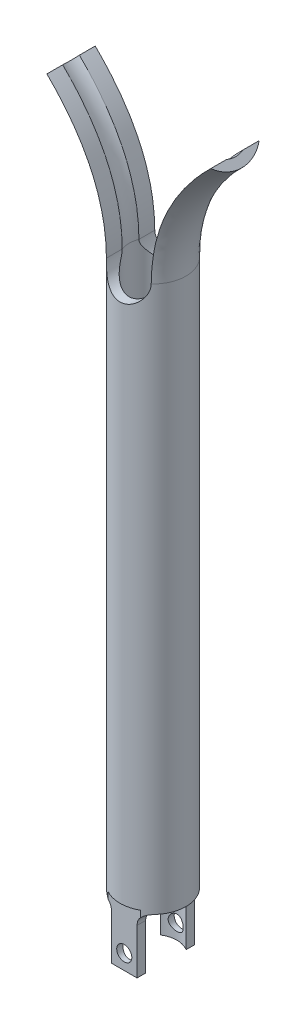
SolidWorks part; units mm, degrees
ref_plane "Front Plane" through (0, 0, 0) normal (0, 0, 1) x (1, 0, 0)
ref_plane "Top Plane" through (0, 0, 0) normal (0, 1, 0) x (1, 0, 0)
ref_plane "Right Plane" through (0, 0, 0) normal (1, 0, 0) x (0, 0, -1)
ref_axis "Axis1" through (0, -45, 0) along (0, 1, 0)
sketch "Sketch1" plane through (0, 0, 0) normal (0, 1, 0) x (1, 0, 0)
  circle A0 centre (0, 0) radius 1.0922
  dimension "D1" = 2.1844
extrude "Extrude-Thin1" add sketch "Sketch1" along normal blind 20 thin thin type one direction reverse wall 0.3
sketch "Sketch2" plane through (0, 20, 0) normal (0, 1, 0) x (1, 0, 0)
  arc A0 (-0.5732, -0.9297) -> (-0.2666, 1.0592) centre (0, 0) cw
  circle A1 centre (0, 0) radius 1.0922 construction
  arc A2 (-0.3687, -0.7011) -> (-0.1565, 0.7766) centre (0, 0) cw
  circle A3 centre (0, 0) radius 0.7922 construction
sketch "Sketch3" plane through (0, 20, 0) normal (0, 1, 0) x (1, 0, 0)
  line L0 (-0.7422, -0.277) -> (-0.7422, -0.8013)
  line L1 (-0.7422, 0.8013) -> (-0.7422, 0.277)
  line L2 (0, 0) -> (-1.0922, 0) construction
  arc A0 (-0.7422, -0.8013) -> (-0.7422, 0.8013) centre (0, 0) cw
  circle A1 centre (0, 0) radius 1.0922 construction
  arc A2 (-0.7422, -0.277) -> (-0.7422, 0.277) centre (0, 0) cw
  circle A5 centre (0, 0) radius 0.7922 construction
  arc A6 (-0.1565, 0.7766) -> (-0.3687, -0.7011) centre (0, 0) ccw construction
  dimension "D1" = 0.35
sketch "Sketch4" plane through (0, 0, 0) normal (0, 0, 1) x (1, 0, 0)
  line L3 (-1.0922, 20) -> (-1.1, 22.8198) construction
  line L4 (-1.1, 22.8198) -> (-4.0922, 25) construction
  spline S0 degree 2 poles (-1.0922, 20) (-1.1, 22.8198) (-4.0922, 25) knots 0 0 0 1 1 1
  dimension "D1" = 5
  dimension "D2" = 3
sweep "Sweep1" add profiles "Sketch3" path "Sketch4"
mirror "Mirror1" about plane through (0, 0, 0) normal (1, 0, 0) of "Sweep1"
sketch "Sketch5" plane through (0, 0, 0) normal (0, 0, 1) x (1, 0, 0)
  line L0 (0.7422, 20) -> (-0.7422, 20) construction
  circle A0 centre (0, 20) radius 0.7422
extrude "Cut-Extrude1" cut sketch "Sketch5" against normal through all both and the other way through all
sketch "Sketch6" plane through (0, 0, 0) normal (0, 0, 1) x (1, 0, 0)
  line L0 (1.0922, 0) -> (1.0922, 20) construction
  line L1 (1.0922, 18.2578) -> (-0.5078, 18.2578)
  line L2 (1.0922, 18.2578) -> (1.0922, 17.4578)
  line L3 (1.0922, 17.4578) -> (-0.5078, 17.4578)
  line L4 (-0.5078, 18.2578) -> (-0.5078, 17.4578)
  arc A1 (-0.7422, 20) -> (0.7422, 20) centre (0, 20) ccw construction
  point P6 (0, 19.2578)
  dimension "D1" = 1
  dimension "D2" = 1.6
  dimension "D3" = 0.8
extrude "Cut-Extrude2" [suppressed] cut sketch "Sketch6" against normal through all both and the other way through all
pattern_linear "LPattern1" [suppressed] count 4 spacing 1.2 of bodies 106
sketch "Sketch7" plane through (0, 0, 0) normal (0, 0, 1) x (1, 0, 0)
  line L0 (-3.9437, 25.3767) -> (-2.6955, 24.3236)
  line L1 (-2.6955, 24.3236) -> (-3.0029, 23.9592)
  line L2 (-3.0029, 23.9592) -> (-4.2334, 24.9973)
  line L3 (-4.2334, 24.9973) -> (-3.9437, 25.3767)
extrude "Cut-Extrude3" cut sketch "Sketch7" against normal blind 1 and the other way blind 1
mirror "Mirror2" about plane through (0, 0, 0) normal (1, 0, 0) of "Cut-Extrude3"
sketch "Sketch10" plane through (0, 0, 0) normal (0, -1, 0) x (1, 0, 0)
  line L0 (4.0304, 0) -> (-3.5992, 0) construction
  line L1 (4.0304, 0.9525) -> (-3.5992, 0.9525)
  line L2 (4.0304, 0.9525) -> (4.0304, -0.9525) construction
  line L3 (4.0304, -0.9525) -> (-3.5992, -0.9525)
  line L4 (-3.5992, 0.9525) -> (-3.5992, -0.9525) construction
  line L5 (1.0922, 0) -> (-1.0922, 0) construction
  line L6 (4.0304, 0.9525) -> (4.0304, 2.3773)
  line L7 (4.0304, 2.3773) -> (-3.5992, 2.3773)
  line L8 (-3.5992, 2.3773) -> (-3.5992, 0.9525)
  line L9 (-3.5992, -0.9525) -> (-3.5992, -2.06)
  line L10 (-3.5992, -2.06) -> (4.0304, -2.06)
  line L11 (4.0304, -2.06) -> (4.0304, -0.9525)
  circle A0 centre (0, 0) radius 1.0922 construction
  dimension "D1" = 1.905
extrude "Cut-Extrude5" cut sketch "Sketch10" against normal blind 2
sketch "Sketch9" plane through (0, 0, 0) normal (0, 0, 1) x (1, 0, 0)
  line L0 (-1.0922, 0) -> (1.0922, 0) construction
  line L1 (-1.0922, 0) -> (1.0922, 0) construction
  line L2 (0, 0) -> (0, 0.5) construction
  circle A0 centre (0, 0.5) radius 0.25
  dimension "D1" = 0.5
  dimension "D2" = 0.5
extrude "Cut-Extrude4" cut sketch "Sketch9" against normal blind 10 and the other way blind 10
sketch "Sketch11" plane through (0, 0, 0) normal (0, 0, 1) x (1, 0, 0)
  line L0 (0.425, 1.5096) -> (0.425, 0)
  line L1 (-1.0922, 0) -> (1.0922, 0) construction
  line L7 (0.8219, 1.9065) -> (3.3932, 1.9065)
  line L8 (0, 0) -> (0, 2.2436) construction
  line L9 (-0.8219, 1.9065) -> (-3.3932, 1.9065)
  line L10 (-0.425, 1.5096) -> (-0.425, 0)
  line L11 (-0.425, 0) -> (-0.425, -3.0838)
  line L12 (-0.425, -3.0838) -> (-3.3932, 1.9065)
  line L13 (3.3932, 1.9065) -> (0.425, -2.0733)
  line L14 (0.425, 0) -> (0.425, -2.0733)
  line L15 (0.5345, 0) -> (-0.5345, 0) construction
  line L16 (0.5345, 0) -> (-0.5345, 0) construction
  arc A0 (0.8219, 1.9065) -> (0.425, 1.5096) centre (0.8219, 1.5096) ccw
  arc A1 (-0.8219, 1.9065) -> (-0.425, 1.5096) centre (-0.8219, 1.5096) cw
  dimension "D3" = 0.3969
  dimension "D1" = 1.9065
extrude "Cut-Extrude10" cut sketch "Sketch11" against normal blind 1.5 and the other way blind 1.5
equation "\"pin_hole_position\"=0.5"
equation "\"D2@Sketch9\"=\"pin_hole_position\""
